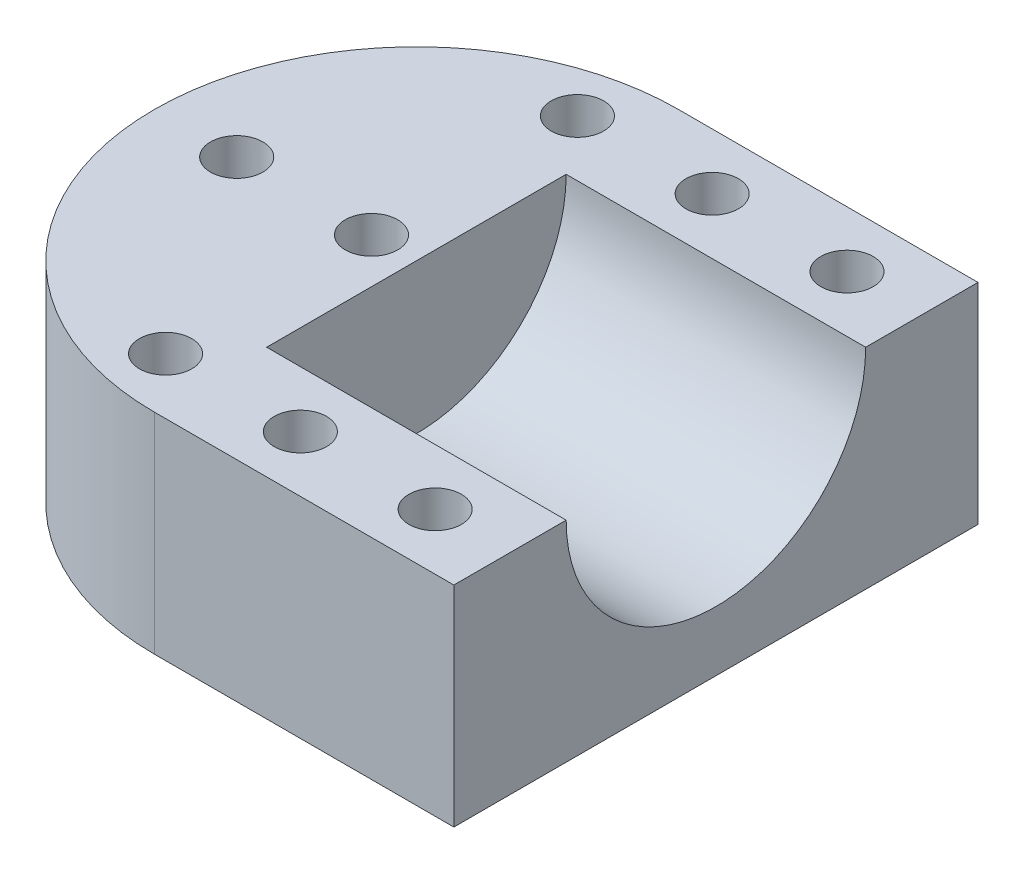
SolidWorks part; units mm, degrees
material "PEI"
ref_plane "Front Plane" through (0, 0, 0) normal (0, 0, 1) x (1, 0, 0)
ref_plane "Top Plane" through (0, 0, 0) normal (0, 1, 0) x (1, 0, 0)
ref_plane "Right Plane" through (0, 0, 0) normal (1, 0, 0) x (0, 0, -1)
sketch "Sketch1" plane through (0, 0, 0) normal (0, 1, 0) x (1, 0, 0)
  line L1 (-20, 17.5) -> (20, 17.5)
  line L2 (-20, 17.5) -> (-20, -17.5)
  line L3 (-20, -17.5) -> (20, -17.5)
  line L4 (20, 17.5) -> (20, -17.5)
  line L5 (-20, 17.5) -> (20, -17.5) construction
  line L6 (-20, -17.5) -> (20, 17.5) construction
  circle A0 centre (0, 0) radius 17.5
  point P0 (0, 0)
  dimension "D1" = 35
  dimension "D2" = 40
extrude "Boss-Extrude1" add sketch "Sketch1" along normal blind 14 and the other way blind 14 contours A0 | A0 L3 L4 L1 region at (10, 0, -17.0969) region at (0, 0, 0)
sketch "Sketch3" plane through (20, 0, 0) normal (1, 0, 0) x (0, 0, -1)
  circle A0 centre (0, 0) radius 10
  dimension "D1" = 20
extrude "Cut-Extrude1" cut sketch "Sketch3" against normal blind 20
sketch "Sketch4" plane through (20, 0, 0) normal (1, 0, 0) x (0, 0, -1)
  line L0 (-29.4883, 0) -> (29.964, 0)
  line L1 (29.964, 0) -> (3.9384, 60.1732)
  line L2 (3.9384, 60.1732) -> (-29.4883, 0)
extrude "Cut-Extrude3" cut sketch "Sketch4" against normal blind 39
sketch "Sketch5" plane through (0, 0, 0) normal (0, 1, 0) x (1, 0, 0)
  line L0 (20, 13.75) -> (-3, 13.75) construction
  line L1 (20, 10) -> (20, 17.5) construction
  line L2 (-3, 13.75) -> (-3, -13.75) construction
  line L3 (-3, -13.75) -> (20, -13.75) construction
  line L4 (20, -17.5) -> (20, -10) construction
  line L5 (-12, 0) -> (0, 0) construction
  circle A0 centre (15, 13.75) radius 1.75
  circle A1 centre (6, 13.75) radius 1.75
  circle A2 centre (-3, 13.75) radius 1.75
  circle A3 centre (-3, 0) radius 1.75
  circle A4 centre (-12, 0) radius 1.75
  circle A5 centre (15, -13.75) radius 1.75
  circle A6 centre (6, -13.75) radius 1.75
  circle A7 centre (-3, -13.75) radius 1.75
  dimension "D1" = 3.5
  dimension "D2" = 5
  dimension "D3" = 9
  dimension "D4" = 9
  dimension "D5" = 12
extrude "Cut-Extrude4" cut sketch "Sketch5" against normal blind 39
sketch "Sketch6" plane through (0, -14, 0) normal (0, -1, 0) x (1, 0, 0)
  circle A0 centre (-3, 13.75) radius 3.25
  circle A1 centre (6, 13.75) radius 3.25
  circle A2 centre (15, 13.75) radius 3.25
  circle A3 centre (-12, 0) radius 3.25
  circle A4 centre (-3, 0) radius 3.25
  circle A5 centre (-3, -13.75) radius 3.25
  circle A6 centre (6, -13.75) radius 3.25
  circle A7 centre (15, -13.75) radius 3.25
  dimension "D1" = 6.5
extrude "Cut-Extrude5" cut sketch "Sketch6" against normal blind 1.5
